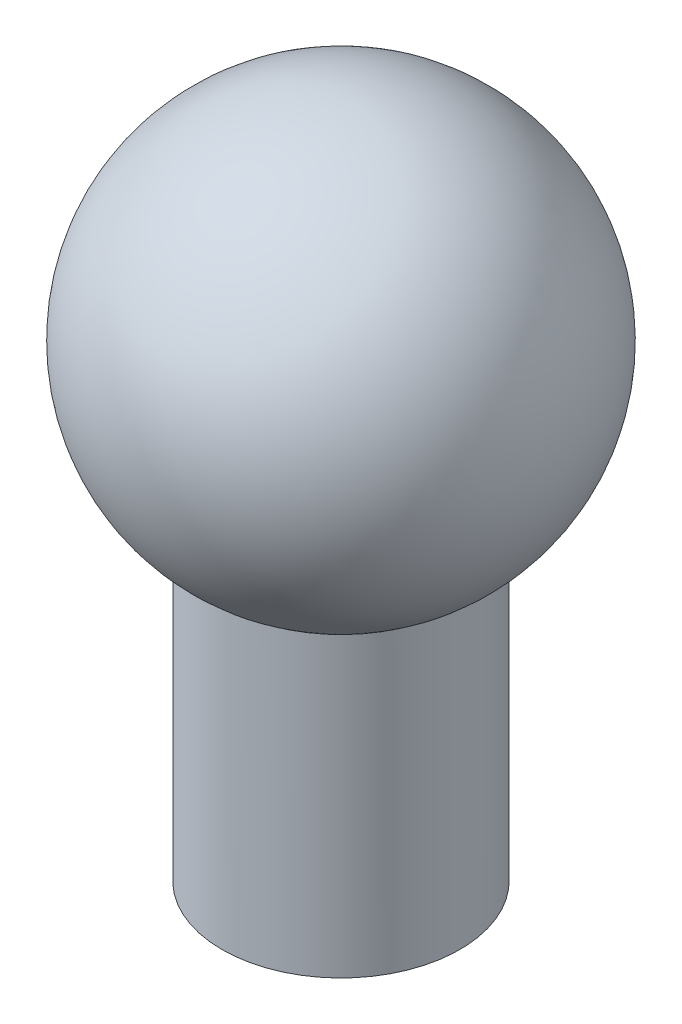
SolidWorks part; units mm, degrees
ref_plane "前视基准面" through (0, 0, 0) normal (0, 0, 1) x (1, 0, 0)
ref_plane "上视基准面" through (0, 0, 0) normal (0, 1, 0) x (1, 0, 0)
ref_plane "右视基准面" through (0, 0, 0) normal (1, 0, 0) x (0, 0, -1)
sketch "草图1" plane through (0, 0, 0) normal (0, 0, 1) x (1, 0, 0)
  line L0 (0, 0) -> (4, 0)
  line L1 (4, 0) -> (4, 10)
  line L2 (0, 0) -> (0, 22.7446)
  arc A0 (0, 22.7446) -> (4, 10) centre (0, 15.7446) cw
  dimension "D1" = 7
  dimension "D2" = 4
  dimension "D3" = 10
revolve "旋转1" add sketch "草图1" angle 360 about L2
ref_point "点1"
